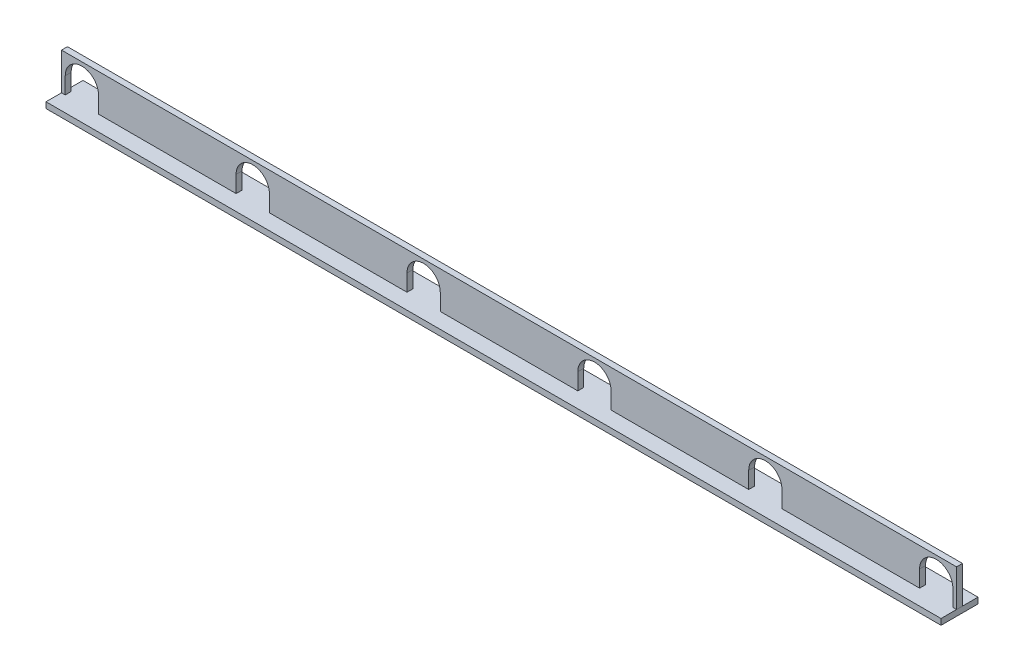
SolidWorks part; units mm, degrees
material "12Х18Н10Т ГОСТ 4543-71"
ref_plane "Спереди" through (0, 0, 0) normal (0, 0, 1) x (1, 0, 0)
ref_plane "Сверху" through (0, 0, 0) normal (0, 1, 0) x (1, 0, 0)
ref_plane "Справа" through (0, 0, 0) normal (1, 0, 0) x (0, 0, -1)
sketch "Эскиз1" plane through (0, 0, 0) normal (0, 0, 1) x (1, 0, 0)
  line L0 (-600, -2.5) -> (-600, -25)
  line L1 (-605, -25) -> (-600, -25)
  line L2 (-605, -25) -> (-605, 25)
  line L3 (-605, 25) -> (605, 25)
  line L4 (605, -25) -> (605, 25)
  line L5 (0, 25) -> (0, -25) construction
  line L6 (-605, 0) -> (605, 0) construction
  line L7 (-555, -2.5) -> (-555, -25)
  line L8 (-555, -25) -> (-369, -25)
  line L9 (-369, -2.5) -> (-369, -25)
  line L10 (-324, -2.5) -> (-324, -25)
  line L11 (-138, -2.5) -> (-138, -25)
  line L12 (-93, -2.5) -> (-93, -25)
  line L13 (93, -2.5) -> (93, -25)
  line L14 (138, -2.5) -> (138, -25)
  line L15 (324, -2.5) -> (324, -25)
  line L16 (369, -2.5) -> (369, -25)
  line L17 (555, -2.5) -> (555, -25)
  line L18 (600, -2.5) -> (600, -25)
  line L19 (-324, -25) -> (-138, -25)
  line L20 (-93, -25) -> (93, -25)
  line L21 (138, -25) -> (324, -25)
  line L22 (369, -25) -> (555, -25)
  line L23 (600, -25) -> (605, -25)
  arc A0 (-555, -2.5) -> (-600, -2.5) centre (-577.5, -2.5) ccw
  arc A1 (-324, -2.5) -> (-369, -2.5) centre (-346.5, -2.5) ccw
  arc A2 (-93, -2.5) -> (-138, -2.5) centre (-115.5, -2.5) ccw
  arc A3 (138, -2.5) -> (93, -2.5) centre (115.5, -2.5) ccw
  arc A4 (369, -2.5) -> (324, -2.5) centre (346.5, -2.5) ccw
  arc A5 (600, -2.5) -> (555, -2.5) centre (577.5, -2.5) ccw
  point P0 (0, 0)
  dimension "D3" = 45
  dimension "D1" = 1210
  dimension "D2" = 50
  dimension "D5" = 5
  dimension "D4" = 6
extrude "Бобышка-Вытянуть1" add sketch "Эскиз1" along normal mid plane 8
sketch "Эскиз2" plane through (0, -25, 0) normal (0, -1, 0) x (1, 0, 0)
  line L0 (605, 4) -> (605, -4) construction
  line L1 (-605, -25) -> (605, -25)
  line L2 (-605, -25) -> (-605, 25)
  line L3 (-605, 25) -> (605, 25)
  line L4 (605, -25) -> (605, 25)
  line L5 (0, 25) -> (0, -25) construction
  line L6 (-605, 0) -> (605, 0) construction
  point P0 (0, 0)
  dimension "D1" = 50
extrude "Бобышка-Вытянуть2" add sketch "Эскиз2" along normal blind 8 separate body
